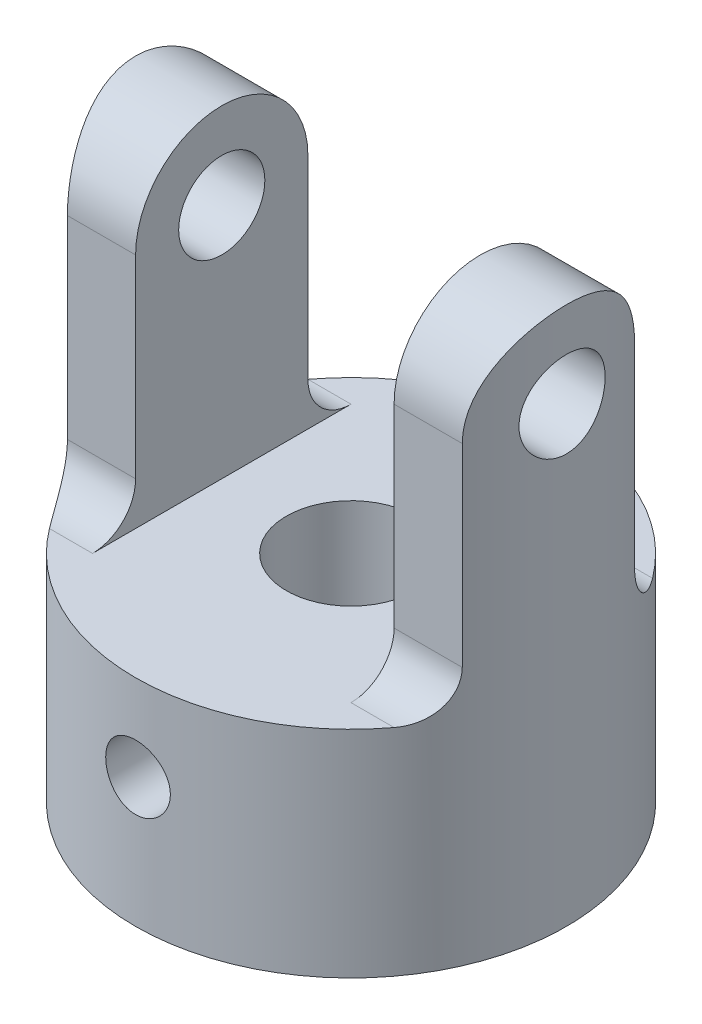
SolidWorks part; units mm, degrees
ref_plane "前基準面" through (0, 0, 0) normal (0, 0, 1) x (1, 0, 0)
ref_plane "上基準面" through (0, 0, 0) normal (0, 1, 0) x (1, 0, 0)
ref_plane "右基準面" through (0, 0, 0) normal (1, 0, 0) x (0, 0, -1)
sketch "草圖1" plane through (0, 0, 0) normal (0, 1, 0) x (1, 0, 0)
  line L1 (-10, -10) -> (10, -10)
  line L2 (-10, -10) -> (-10, 10)
  line L3 (-10, 10) -> (10, 10)
  line L4 (10, -10) -> (10, 10)
  line L5 (-10, -10) -> (10, 10) construction
  line L6 (-10, 10) -> (10, -10) construction
  point P0 (0, 0)
  dimension "D1" = 20
  dimension "D2" = 20
extrude "填料-伸長1" add sketch "草圖1" along normal blind 10
sketch "草圖2" plane through (0, 0, 0) normal (1, 0, 0) x (0, 0, -1)
  line L0 (4, 10) -> (4, 21)
  line L1 (10, 10) -> (-10, 10) construction
  line L2 (10, 0) -> (-10, 0) construction
  line L3 (-4, 21) -> (-4, 10)
  line L4 (0, 21.6014) -> (0, -6.239) construction
  line L5 (4, 10) -> (-4, 10)
  arc A0 (4, 21) -> (-4, 21) centre (0, 21) ccw
  circle A1 centre (0, 21) radius 2
  dimension "D1" = 4
  dimension "D2" = 4
  dimension "D3" = 21
extrude "填料-伸長2" add sketch "草圖2" along normal mid plane 20
extrude "除料-伸長1" cut sketch "草圖2<2>" against normal mid plane 12
sketch "草圖2<2>" plane through (0, 0, 0) normal (1, 0, 0) x (0, 0, -1) same geometry as "草圖2"
sketch "草圖4" plane through (0, 0, 0) normal (0, 1, 0) x (1, 0, 0)
  circle A0 centre (0, 0) radius 10
  dimension "D1" = 20
extrude "除料-伸長2" cut sketch "草圖4" along normal through all flip side to cut
sketch "草圖5" plane through (0, 0, 0) normal (0, -1, 0) x (1, 0, 0)
  circle A0 centre (0, 0) radius 3
  dimension "D1" = 6
extrude "除料-伸長3" cut sketch "草圖5" against normal through all
sketch "草圖6" plane through (0, 0, 0) normal (0, 0, 1) x (1, 0, 0)
  line L0 (-10, 0) -> (10, 0) construction
  circle A0 centre (0, 6) radius 1.5
  dimension "D1" = 3
  dimension "D2" = 6
extrude "除料-伸長4" cut sketch "草圖6" along normal through all
fillet "圓角1" radius 2 4 edges at (-7.5826, 10, -4) (7.5826, 10, -4) (-7.5826, 10, 4) (7.5826, 10, 4)
